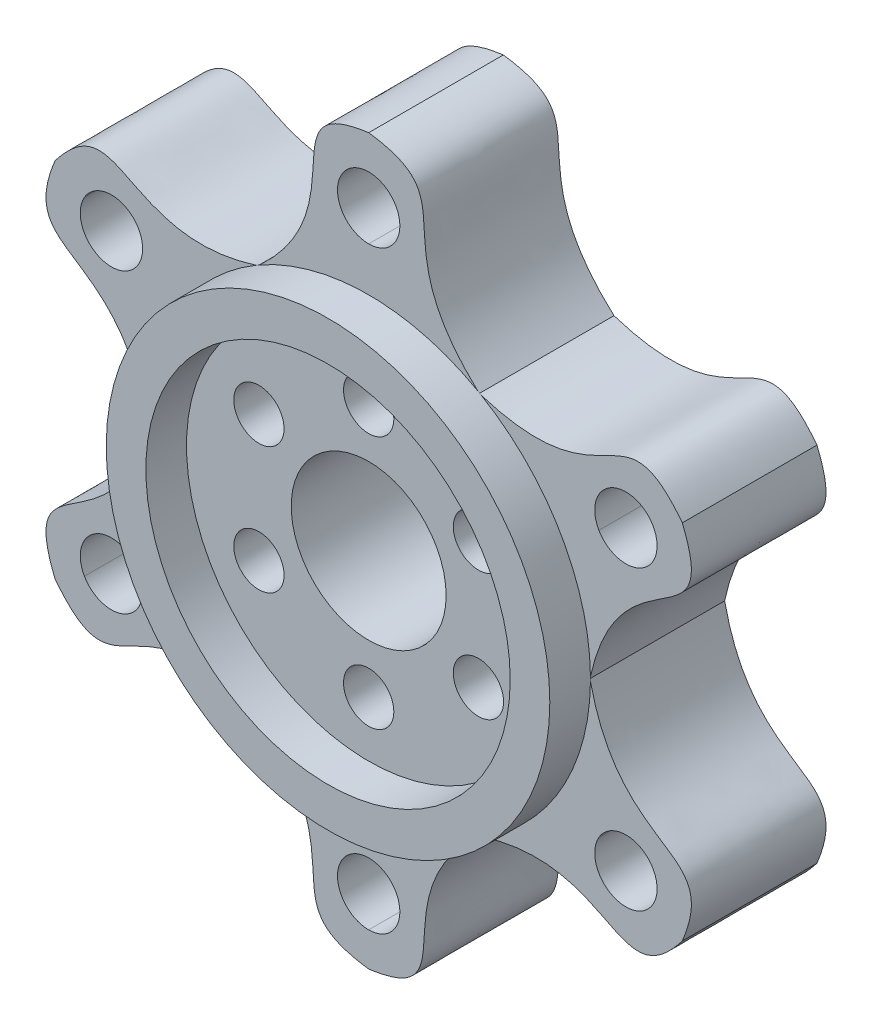
SolidWorks part; units mm, degrees
ref_plane "Front Plane" through (0, 0, 0) normal (0, 0, 1) x (1, 0, 0)
ref_plane "Top Plane" through (0, 0, 0) normal (0, 1, 0) x (1, 0, 0)
ref_plane "Right Plane" through (0, 0, 0) normal (1, 0, 0) x (0, 0, -1)
sketch "Sketch1" plane through (0, 0, 0) normal (0, 0, 1) x (1, 0, 0)
  line L0 (0, -55) -> (0, 55) construction
  line L1 (0, 0) -> (0, 45.72) construction
  circle A0 centre (0, 0) radius 9.779
  circle A1 centre (0, 0) radius 45.72
  circle A2 centre (0, 16.002) radius 3.175
  circle A3 centre (13.8581, 8.001) radius 3.175
  circle A4 centre (13.8581, -8.001) radius 3.175
  circle A5 centre (0, -16.002) radius 3.175
  circle A6 centre (-13.8581, -8.001) radius 3.175
  circle A7 centre (-13.8581, 8.001) radius 3.175
  circle A8 centre (0, 37.5) radius 3.937
  circle A10 centre (32.476, 18.75) radius 3.937
  circle A11 centre (32.476, -18.75) radius 3.937
  circle A12 centre (0, -37.5) radius 3.937
  circle A13 centre (-32.476, -18.75) radius 3.937
  circle A14 centre (-32.476, 18.75) radius 3.937
  point P21 (0, 0)
  point P36 (0, 0)
  dimension "D1" = 19.558
  dimension "D2" = 91.44
  dimension "D3" = 6.35
  dimension "D6" = 7.874
  dimension "D4" = 16.002
  dimension "D8" = 37.5
  dimension "D5" = 6
  dimension "D7" = 6
extrude "Boss-Extrude3" add sketch "Sketch1" along normal blind 17
sketch "Sketch2" plane through (0, 0, 17) normal (0, 0, 1) x (1, 0, 0)
  line L0 (0, -55) -> (0, 55) construction
  line L1 (-32.476, 18.75) -> (0, 37.5) construction
  line L2 (-16.238, 28.125) -> (-4.8895, 8.4689) construction
  line L3 (16.1981, 28.148) -> (4.8496, 8.4918) construction
  line L6 (32.476, -18.75) -> (32.476, 18.75) construction
  line L7 (32.476, 18.75) -> (0, 37.5) construction
  line L8 (55, 0) -> (-55, 0) construction
  circle A0 centre (0, 0) radius 27.94 construction
  circle A1 centre (0, 0) radius 45.72 construction
  circle A2 centre (0, 0) radius 9.779 construction
  circle A3 centre (0, 0) radius 45.72
  spline S0 degree 3 poles (-13.97, 24.1967) (-0.9195, 35.9832) (-13.1193, 43.9586) (0, 45.72) knots 0 0 0 0 1 1 1 1
  spline S1 degree 3 poles (13.97, 24.1967) (0.9195, 35.9832) (13.1193, 43.9586) (0, 45.72) knots 0 0 0 0 1 1 1 1
  spline S2 degree 3 poles (-27.94, 0) (-31.6221, 17.1953) (-44.6289, 10.6177) (-39.5947, 22.86) knots 0 0 0 0 1 1 1 1
  spline S3 degree 3 poles (-13.97, 24.1967) (-30.7026, 18.7879) (-31.5096, 33.3409) (-39.5947, 22.86) knots 0 0 0 0 1 1 1 1
  spline S4 degree 3 poles (-13.97, -24.1967) (-30.7026, -18.7879) (-31.5096, -33.3409) (-39.5947, -22.86) knots 0 0 0 0 1 1 1 1
  spline S5 degree 3 poles (-27.94, 0) (-31.6221, -17.1953) (-44.6289, -10.6177) (-39.5947, -22.86) knots 0 0 0 0 1 1 1 1
  spline S6 degree 3 poles (13.97, -24.1967) (30.7026, -18.7879) (31.5096, -33.3409) (39.5947, -22.86) knots 0 0 0 0 1 1 1 1
  spline S7 degree 3 poles (27.94, 0) (31.6221, -17.1953) (44.6289, -10.6177) (39.5947, -22.86) knots 0 0 0 0 1 1 1 1
  spline S8 degree 3 poles (13.97, -24.1967) (0.9195, -35.9832) (13.1193, -43.9586) (0, -45.72) knots 0 0 0 0 1 1 1 1
  spline S9 degree 3 poles (-13.97, -24.1967) (-0.9195, -35.9832) (-13.1193, -43.9586) (0, -45.72) knots 0 0 0 0 1 1 1 1
  spline S10 degree 3 poles (27.94, 0) (31.6221, 17.1953) (44.6289, 10.6177) (39.5947, 22.86) knots 0 0 0 0 1 1 1 1
  spline S11 degree 3 poles (13.97, 24.1967) (30.7026, 18.7879) (31.5096, 33.3409) (39.5947, 22.86) knots 0 0 0 0 1 1 1 1
  point P5 (-16.238, 28.125)
  point P6 (16.1981, 28.148)
  circle M8 centre (0, 0) radius 45.72
  dimension "D1" = 55.88
  dimension "D2" = 18.796
extrude "Cut-Extrude1" cut sketch "Sketch2" against normal blind 22.86 contours S1 S11 M8 | S5 S2 A3 | S10 S7 A3 | S6 S8 A3 | S9 S4 M8 | S3 S0 M8 region at (38.1245, 0, 17) region at (19.0622, 33.0168, 17) region at (19.0622, -33.0168, 17) region at (-19.0622, 33.0168, 17) region at (-19.0622, -33.0168, 17) region at (-38.1245, 0, 17)
sketch "Sketch4" plane through (0, 0, 17) normal (0, 0, 1) x (1, 0, 0)
  circle A0 centre (0, 0) radius 9.779 construction
  circle A1 centre (0, 0) radius 9.779 construction
  circle A2 centre (0, 0) radius 28
  circle A3 centre (0, 0) radius 23
  dimension "D1" = 56
  dimension "D2" = 46
extrude "Boss-Extrude4" add sketch "Sketch4" along normal blind 5.1308 contours A2 | A3
ref_plane "Plane1" through (0, 0, 0) normal (1, 0, 0) x (0, 0, -1)
ref_plane "Plane2" through (0, 0, 0) normal (-0.5, -0.866, 0) x (-0.866, 0.5, 0)
ref_plane "Plane3" through (0, 0, 0) normal (-0.5, 0.866, 0) x (0.866, 0.5, 0)
split line "Split Line1"
split line "Split Line2"
split line "Split Line3"
ref_axis "Axis1" through (0, 0, 17) along (0, 0, -1)
